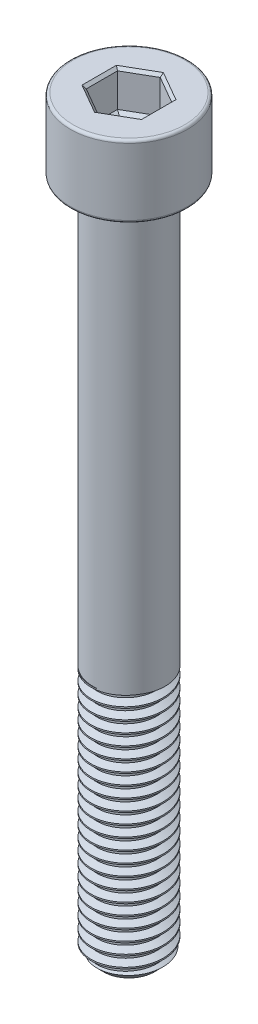
SolidWorks part; units mm, degrees
material "AISI Type A2 Tool Steel"
ref_plane "Front Plane" through (0, 0, 0) normal (0, 0, 1) x (1, 0, 0)
ref_plane "Top Plane" through (0, 0, 0) normal (0, 1, 0) x (1, 0, 0)
ref_plane "Right Plane" through (0, 0, 0) normal (1, 0, 0) x (0, 0, -1)
sketch "Sketch1" plane through (0, 0, 0) normal (0, 1, 0) x (1, 0, 0)
  circle A0 centre (0, 0) radius 4
  dimension "D1" = 8
extrude "Boss-Extrude1" add sketch "Sketch1" along normal blind 28
thread "Thread1" pitch 1.25 method cut profile "Thread Profile1" start angle 0, offset 2, length 0, pitch 1.25, diameter 8
ref_plane "Plane1" through (-4, 30, 0) normal (0, 0, 1) x (-1, 0, 0)
sketch "Thread Profile1" plane through (-4, 30, 0) normal (0, 0, 1) x (-1, 0, 0)
  line L0 (0, 0) -> (0, 1.25) construction
  line L11 (0, 0) -> (0, 1.0937)
  line L12 (0, 1.0937) -> (-0.6766, 0.7031)
  line L13 (-0.6766, 0.7031) -> (-0.6766, 0.3906)
  line L15 (-0.6766, 0.3906) -> (0, 0)
  line L17 (-0.6766, 0.5469) -> (0, 0.5469) construction
  point P2 (0, 0)
  dimension "Pitch" = 1.25
  dimension "Profile_Angle" = 60
  dimension "Profile_Land" = 0.3125
  dimension "Profile_Height" = 0.6766
sketch "Sketch2" plane through (0, 28, 0) normal (0, 1, 0) x (1, 0, 0)
  circle A0 centre (0, 0) radius 4
  dimension "D1" = 8
extrude "Boss-Extrude2" add sketch "Sketch2" along normal blind 47
sketch "Sketch5" plane through (0, 75, 0) normal (0, 1, 0) x (1, 0, 0)
  circle A0 centre (0, 0) radius 6.5
  dimension "D1" = 13
extrude "Boss-Extrude3" add sketch "Sketch5" along normal blind 8
sketch "Sketch6" plane through (0, 0, 0) normal (0, 0, 1) x (1, 0, 0)
  line L0 (0, 0) -> (0, 0.7245) construction
  line L1 (0, 0) -> (4.01, 0) construction
  line L2 (4.01, 0) -> (4.01, 1.2)
  line L3 (4.01, 1.2) -> (2.81, 0)
  line L4 (2.81, 0) -> (4.01, 0)
  dimension "D1" = 1.2
  dimension "D2" = 45
  dimension "D3" = 4.01
revolve "Cut-Revolve1" cut sketch "Sketch6" angle 360 about L0
fillet "Fillet1" radius 0.3 2 edges at (0, 75, 6.5) (0, 83, 6.5)
sketch "Sketch7" plane through (0, 83, 0) normal (0, 1, 0) x (1, 0, 0)
  line L1 (0, 3.4641) -> (-3, 1.7321)
  line L2 (-3, 1.7321) -> (-3, -1.7321)
  line L3 (-3, -1.7321) -> (0, -3.4641)
  line L4 (0, -3.4641) -> (3, -1.7321)
  line L5 (3, -1.7321) -> (3, 1.7321)
  line L6 (3, 1.7321) -> (0, 3.4641)
  circle A0 centre (0, 0) radius 3 construction
  dimension "D1" = 6
extrude "Cut-Extrude1" cut sketch "Sketch7" against normal blind 4
chamfer "Chamfer1" distance 0.3 angle 45 6 edges at (-3, 83, 0) (-1.5, 83, 2.5981) (1.5, 83, 2.5981) (3, 83, 0) (1.5, 83, -2.5981) (-1.5, 83, -2.5981)
sketch "Sketch8" plane through (0, 79, 0) normal (0, 1, 0) x (1, 0, 0)
  line L1 (0, 3.4641) -> (-3, 1.7321)
  line L2 (-3, 1.7321) -> (-3, -1.7321)
  line L3 (-3, -1.7321) -> (0, -3.4641)
  line L4 (0, -3.4641) -> (3, -1.7321)
  line L5 (3, -1.7321) -> (3, 1.7321)
  line L6 (3, 1.7321) -> (0, 3.4641)
  circle A0 centre (0, 0) radius 3 construction
extrude "Cut-Extrude2" cut sketch "Sketch8" against normal blind 0.4 draft 60
